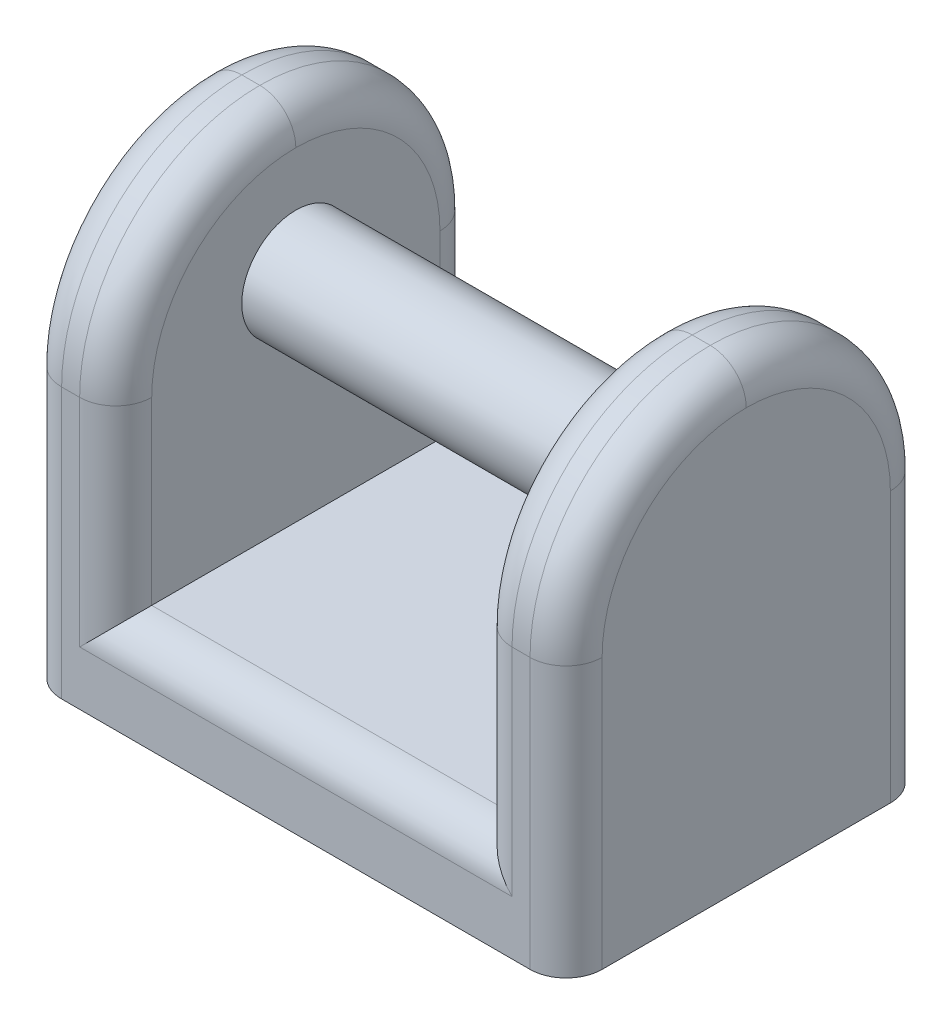
SolidWorks part; units mm, degrees
ref_plane "Alzado" through (0, 0, 0) normal (0, 0, 1) x (1, 0, 0)
ref_plane "Planta" through (0, 0, 0) normal (0, 1, 0) x (1, 0, 0)
ref_plane "Vista lateral" through (0, 0, 0) normal (1, 0, 0) x (0, 0, -1)
sketch "Croquis1" plane through (0, 0, 0) normal (0, 0, 1) x (1, 0, 0)
  line L0 (0, 0) -> (0, 50)
  line L1 (0, 50) -> (12.5, 50)
  line L2 (12.5, 50) -> (12.5, 0)
  line L3 (12.5, 0) -> (62.5, 0)
  line L4 (62.5, 0) -> (62.5, 50)
  line L5 (62.5, 50) -> (75, 50)
  line L6 (75, 50) -> (75, -12.5)
  line L7 (75, -12.5) -> (0, -12.5)
  line L8 (0, -12.5) -> (0, 0)
extrude "Saliente-Extruir1" add sketch "Croquis1" along normal blind 50 contours L7 L8 L0 L1 L2 L3 L4 L5 L6
sketch "Croquis2" plane through (75, 0, 0) normal (1, 0, 0) x (0, 0, -1)
  circle A0 centre (-25, 30) radius 7.5
extrude "Saliente-Extruir2" add sketch "Croquis2" against normal blind 75
fillet "Redondeo1" radius 25 4 edges at (6.25, 50, 0) (6.25, 50, 50) (68.75, 50, 50) (68.75, 50, 0)
fillet "Redondeo2" radius 5 18 edges at (62.5, 42.6777, 42.6777) (62.5, 42.6777, 7.3223) (12.5, 42.6777, 42.6777) (12.5, 42.6777, 7.3223) (0, 42.6777, 42.6777) (0, 42.6777, 7.3223) (75, 42.6777, 42.6777) (75, 42.6777, 7.3223) (75, 6.25, 50) (62.5, 12.5, 50) (12.5, 12.5, 50) (0, 6.25, 50) (37.5, 0, 0) (62.5, 12.5, 0) (12.5, 12.5, 0) (0, 6.25, 0) (75, 6.25, 0) (37.5, 0, 50)
